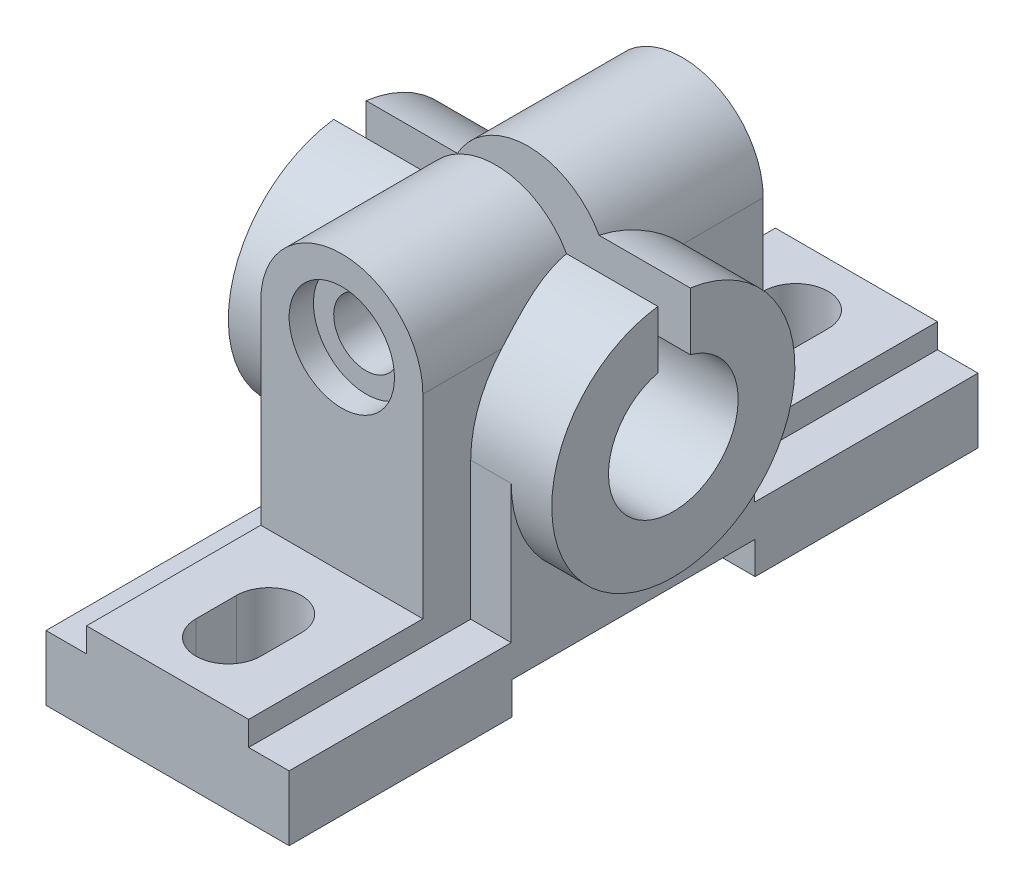
SolidWorks part; units mm, degrees
ref_plane "前视基准面" through (0, 0, 0) normal (0, 0, 1) x (1, 0, 0)
ref_plane "上视基准面" through (0, 0, 0) normal (0, 1, 0) x (1, 0, 0)
ref_plane "右视基准面" through (0, 0, 0) normal (1, 0, 0) x (0, 0, -1)
other "Configuration Table"
sketch "草图1" plane through (0, 0, 0) normal (0, 0, 1) x (1, 0, 0)
  line L1 (-3.7231, 12.014) -> (26.2769, 12.014)
  line L2 (-3.7231, 12.014) -> (-3.7231, 4.014)
  line L3 (-3.7231, 4.014) -> (26.2769, 4.014)
  line L4 (26.2769, 12.014) -> (26.2769, 4.014)
  line L5 (1.2769, 12.014) -> (21.2769, 12.014)
  line L6 (1.2769, 12.014) -> (1.2769, 15.014)
  line L7 (1.2769, 15.014) -> (21.2769, 15.014)
  line L8 (21.2769, 12.014) -> (21.2769, 15.014)
  dimension "D1" = 30
  dimension "D2" = 8
  dimension "D3" = 20
  dimension "D4" = 3
  dimension "D5" = 5
extrude "凸台-拉伸1" add sketch "草图1" against normal blind 85 contours L4 L1 L2 L3 | L1 L8 L7 L6 region at (11.2769, 8.014, 0) region at (11.2769, 13.514, 0)
sketch "草图2" plane through (0, 15.014, 0) normal (0, 1, 0) x (1, 0, 0)
  line L0 (21.2769, 85) -> (21.2769, 0) construction
  line L2 (7.2769, 12.5) -> (7.2769, 7.5)
  line L4 (15.2769, 12.5) -> (15.2769, 7.5)
  line L5 (1.2769, 0) -> (21.2769, 0) construction
  line L7 (7.2769, 77.5) -> (7.2769, 72.5)
  line L9 (15.2769, 77.5) -> (15.2769, 72.5)
  line L10 (21.2769, 85) -> (21.2769, 0) construction
  line L11 (1.2769, 85) -> (21.2769, 85) construction
  arc A0 (7.2769, 12.5) -> (15.2769, 12.5) centre (11.2769, 12.5) cw
  arc A1 (7.2769, 7.5) -> (15.2769, 7.5) centre (11.2769, 7.5) ccw
  arc A2 (7.2769, 77.5) -> (15.2769, 77.5) centre (11.2769, 77.5) cw
  arc A3 (7.2769, 72.5) -> (15.2769, 72.5) centre (11.2769, 72.5) ccw
  dimension "D1" = 5
  dimension "D2" = 8
  dimension "D3" = 10
  dimension "D4" = 7.5
  dimension "D5" = 10
  dimension "D6" = 7.5
sketch "草图3" plane through (26.2769, 0, 0) normal (1, 0, 0) x (0, 0, -1)
  line L0 (85, 4.014) -> (0, 4.014) construction
  line L1 (27.5, 4.014) -> (57.5, 4.014)
  line L2 (27.5, 4.014) -> (27.5, 8.014)
  line L3 (27.5, 8.014) -> (57.5, 8.014)
  line L4 (57.5, 4.014) -> (57.5, 8.014)
  line L5 (85, 12.014) -> (85, 4.014) construction
  dimension "D1" = 30
  dimension "D2" = 4
  dimension "D3" = 27.5
ref_plane "基准面1" through (0, 0, -21.5) normal (0, 0, 1) x (1, 0, 0)
sketch "草图4" plane through (0, 0, -21.5) normal (0, 0, 1) x (1, 0, 0)
  line L1 (1.2769, 15.014) -> (21.2769, 15.014)
  line L2 (1.2769, 15.014) -> (1.2769, 39.014)
  line L4 (21.2769, 15.014) -> (21.2769, 39.014)
  arc A1 (1.2769, 39.014) -> (21.2769, 39.014) centre (11.2769, 39.014) cw
  dimension "D1" = 20
  dimension "D2" = 24
extrude "凸台-拉伸2" add sketch "草图4" against normal blind 42
extrude "切除-拉伸1" cut sketch "草图3" against normal blind 42
extrude "切除-拉伸2" cut sketch "草图2" against normal blind 42
sketch "草图17" plane through (0, 0, -21.5) normal (0, 0, 1) x (1, 0, 0)
  line L0 (21.2769, 15.014) -> (21.2769, 39.014) construction
  line L1 (1.2769, 15.014) -> (21.2769, 15.014) construction
  circle A0 centre (11.2769, 39.014) radius 6.5
  dimension "D1" = 13
  dimension "D2" = 10
  dimension "D3" = 24
extrude "切除-拉伸5" cut sketch "草图17" against normal blind 3 contours A0
sketch "草图19" plane through (0, 0, -63.5) normal (0, 0, -1) x (-1, 0, 0)
  line L0 (-1.2769, 15.014) -> (-21.2769, 15.014) construction
  line L1 (-21.2769, 15.014) -> (-21.2769, 39.014) construction
  circle A0 centre (-11.2769, 39.014) radius 6.5
  dimension "D1" = 13
  dimension "D2" = 24
  dimension "D3" = 10
extrude "切除-拉伸6" cut sketch "草图19" against normal blind 3
sketch "草图20" plane through (0, 0, -60.5) normal (0, 0, -1) x (-1, 0, 0)
  line L0 (-1.2769, 15.014) -> (-21.2769, 15.014) construction
  line L1 (-1.2769, 39.014) -> (-1.2769, 15.014) construction
  circle A0 centre (-11.2769, 39.014) radius 4
  point P6 (-11.2769, 15.014)
  dimension "D1" = 8
  dimension "D2" = 24
  dimension "D3" = 10
extrude "切除-拉伸7" cut sketch "草图20" against normal blind 85 contours A0
ref_plane "基准面5" through (26.2769, 0, 0) normal (1, 0, 0) x (0, 0, -1)
sketch "草图26" plane through (26.2769, 0, 0) normal (1, 0, 0) x (0, 0, -1)
  line L1 (27.4052, 12.014) -> (57.4052, 12.014)
  line L2 (27.4052, 12.014) -> (27.4052, 29.014)
  line L4 (57.4052, 12.014) -> (57.4052, 29.014)
  line L6 (27.4052, 17.5044) -> (27.4052, 50006.7232) construction
  arc A0 (27.4052, 29.014) -> (57.4052, 29.014) centre (42.4052, 29.014) cw
  point P4 (27.4052, 17.5044)
  point P7 (0, 0)
  dimension "D1" = 30
  dimension "D2" = 17
  dimension "D3" = 0
extrude "凸台-拉伸7" add sketch "草图26" against normal up to next
sketch "草图27" plane through (-3.7231, 0, 0) normal (-1, 0, 0) x (0, 0, 1)
  line L0 (-57.5, 12.014) -> (-27.5, 12.014)
  line L1 (-57.5, 12.014) -> (-57.5, 29.014)
  line L2 (-27.5, 12.014) -> (-27.5, 29.014)
  line L3 (-57.5, -11.1551) -> (-57.5, 49988.8449) construction
  line L4 (-85, 12.014) -> (0, 12.014) construction
  line L5 (-57.5, 8.014) -> (-57.5, 4.014) construction
  arc A0 (-57.5, 29.014) -> (-27.5, 29.014) centre (-42.5, 29.014) cw
  dimension "D1" = 0
  dimension "D2" = 0
extrude "凸台-拉伸8" add sketch "草图27" against normal up to next
sketch "草图28" plane through (26.2769, 0, 0) normal (1, 0, 0) x (0, 0, -1)
  circle A0 centre (42.4052, 29.014) radius 15
extrude "凸台-拉伸9" add sketch "草图28" along normal blind 5
sketch "草图30" plane through (-3.7231, 0, 0) normal (-1, 0, 0) x (0, 0, 1)
  circle A0 centre (-56.2965, 34.8019) radius 0.0386
sketch "草图31" plane through (-3.7231, 0, 0) normal (-1, 0, 0) x (0, 0, 1)
  circle A0 centre (-42.5, 29.014) radius 15
extrude "凸台-拉伸13" add sketch "草图31" along normal blind 5
sketch "草图32" plane through (31.2769, 0, 0) normal (1, 0, 0) x (0, 0, -1)
  circle A2 centre (42.4052, 29.014) radius 8
  circle A3 centre (42.4052, 29.014) radius 8
  dimension "D1" = 7
extrude "切除-拉伸8" cut sketch "草图32" against normal through all
sketch "草图33" plane through (26.2769, 0, 0) normal (1, 0, 0) x (0, 0, -1)
  line L0 (21.5, 39.014) -> (63.5, 39.014) construction
  line L2 (40.5, 52.1896) -> (44.5, 52.1896)
  line L3 (40.5, 52.1896) -> (40.5, 25.8383)
  line L4 (40.5, 25.8383) -> (44.5, 25.8383)
  line L5 (44.5, 52.1896) -> (44.5, 25.8383)
  line L6 (40.5, 52.1896) -> (44.5, 25.8383) construction
  line L7 (40.5, 25.8383) -> (44.5, 52.1896) construction
  point P5 (42.5, 39.014)
  dimension "D1" = 4
extrude "切除-拉伸10" cut sketch "草图33" against normal through all and the other way blind 15
